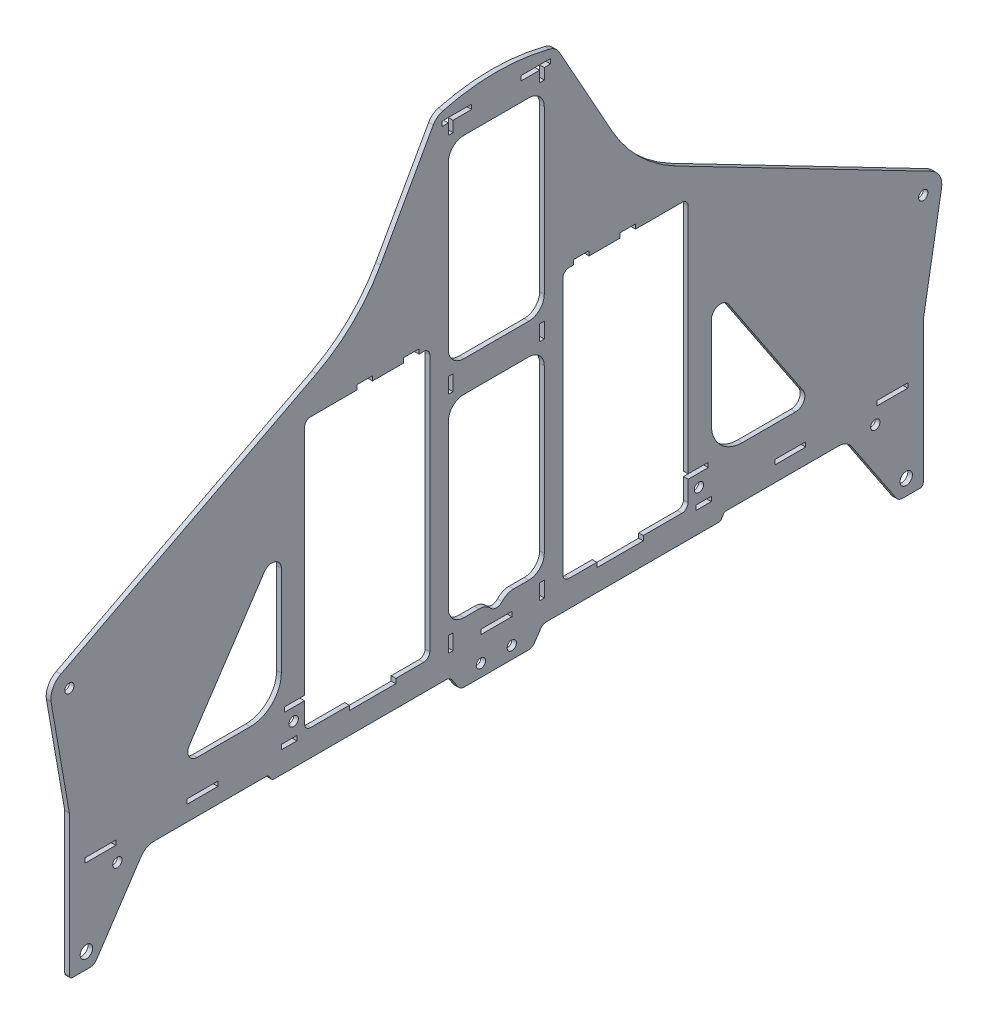
SolidWorks part; units mm, degrees
material "1023 Arkusz stali węglowej (SS)"
ref_plane "Płaszczyzna przednia" through (0, 0, 0) normal (0, 0, 1) x (1, 0, 0)
ref_plane "Płaszczyzna górna" through (0, 0, 0) normal (0, 1, 0) x (1, 0, 0)
ref_plane "Płaszczyzna prawa" through (0, 0, 0) normal (1, 0, 0) x (0, 0, -1)
sketch "Szkic1" plane through (0, 0, 0) normal (1, 0, 0) x (0, 0, -1)
  line L0 (-28.5915, -81.3449) -> (-24.8935, -86.8919)
  line L1 (-20.7333, -89.1184) -> (-0.0759, -89.1184)
  line L2 (-221.3907, -75.1184) -> (-148.664, -75.1184)
  line L3 (-143.8566, -79.1184) -> (-32.7518, -79.1184)
  line L4 (-145.5207, -78.2278) -> (-146.9999, -76.009)
  line L5 (-40.799, 235.6314) -> (-74.9912, 174.2495)
  line L6 (-276.0759, -123.1184) -> (-276.0759, -32.1184)
  line L7 (-258.5915, -122.8919) -> (-229.7112, -79.5714)
  line L8 (-274.0759, -125.1184) -> (-262.7518, -125.1184)
  line L9 (-116.3615, 134.116) -> (-281.5947, 48.5372)
  line L10 (-276.0759, -32.1184) -> (-287.9891, 36.4416)
  line L11 (-50.0759, 114.8816) -> (-50.0759, 111.8816)
  line L12 (-80.0759, 114.8816) -> (-80.0759, 111.8816)
  line L13 (-60.0759, 114.8816) -> (-60.0759, 111.8816)
  line L14 (-129.0759, -62.1184) -> (-129.0759, -65.1184)
  line L15 (-139.0759, -62.1184) -> (-139.0759, -65.1184)
  line L16 (-137.0759, -42.1184) -> (-124.0759, -42.1184)
  line L17 (-137.0759, -45.1184) -> (-124.0759, -45.1184)
  line L18 (-137.0759, -42.1184) -> (-137.0759, -45.1184)
  line L19 (-60.0759, 114.8816) -> (-50.0759, 114.8816)
  line L20 (-90.0759, 111.8816) -> (-90.0759, 114.8816)
  line L21 (-90.0759, 114.8816) -> (-80.0759, 114.8816)
  line L22 (-139.0759, -62.1184) -> (-129.0759, -62.1184)
  line L23 (-139.0759, -65.1184) -> (-129.0759, -65.1184)
  line L24 (-95.0759, -65.1184) -> (-65.0759, -65.1184)
  line L25 (-95.0759, -62.1184) -> (-95.0759, -65.1184)
  line L26 (-65.0759, -65.1184) -> (-65.0759, -62.1184)
  line L27 (-10.0759, -62.1184) -> (-10.0759, -65.1184)
  line L28 (-0.0759, -62.1184) -> (-10.0759, -62.1184)
  line L29 (-10.0759, -65.1184) -> (-0.0759, -65.1184)
  line L30 (-266.0759, -62.1184) -> (-266.0759, -65.1184)
  line L31 (-246.0759, -62.1184) -> (-246.0759, -65.1184)
  line L32 (-266.0759, -65.1184) -> (-246.0759, -65.1184)
  line L33 (-266.0759, -62.1184) -> (-246.0759, -62.1184)
  line L34 (-35.0759, 234.8816) -> (-16.0759, 234.8816)
  line L35 (-28.0759, 231.8816) -> (-16.0759, 231.8816)
  line L36 (-31.0759, 231.8816) -> (-31.0759, 224.8816)
  line L37 (-16.0759, 234.8816) -> (-16.0759, 231.8816)
  line L38 (-28.0759, 224.8816) -> (-31.0759, 224.8816)
  line L39 (-28.0759, 231.8816) -> (-28.0759, 224.8816)
  line L40 (-21.0759, -50.1184) -> (-11.2562, -50.1184)
  line L41 (-31.0759, 64.8816) -> (-31.0759, -40.1184)
  line L42 (-0.0759, 219.8816) -> (-21.0759, 219.8816)
  line L43 (-31.0759, 209.8816) -> (-31.0759, 104.8816)
  line L44 (-0.0759, 74.8816) -> (-21.0759, 74.8816)
  line L45 (-21.0759, 94.8816) -> (-0.0759, 94.8816)
  line L46 (-159.0759, -42.1184) -> (-193.5314, -42.1184)
  line L47 (-139.0759, 36.5649) -> (-139.0759, -22.1184)
  line L48 (-198.5237, -32.7902) -> (-150.0682, 39.8931)
  line L49 (-35.0759, 231.8816) -> (-31.0759, 231.8816)
  line L50 (-35.0759, 234.8816) -> (-35.0759, 231.8816)
  line L51 (28.4398, -81.3449) -> (24.7418, -86.8919)
  line L52 (20.5816, -89.1184) -> (-0.0759, -89.1184)
  line L53 (221.239, -75.1184) -> (148.5123, -75.1184)
  line L54 (143.7049, -79.1184) -> (32.6001, -79.1184)
  line L55 (145.369, -78.2278) -> (146.8482, -76.009)
  line L56 (40.6473, 235.6314) -> (74.8395, 174.2495)
  line L57 (275.9241, -123.1184) -> (275.9241, -32.1184)
  line L58 (258.4398, -122.8919) -> (229.5595, -79.5714)
  line L59 (273.9241, -125.1184) -> (262.6001, -125.1184)
  line L60 (116.2098, 134.116) -> (281.443, 48.5372)
  line L61 (275.9241, -32.1184) -> (287.8374, 36.4416)
  line L62 (49.9241, 114.8816) -> (49.9241, 111.8816)
  line L63 (79.9241, 114.8816) -> (79.9241, 111.8816)
  line L64 (59.9241, 114.8816) -> (59.9241, 111.8816)
  line L65 (128.9241, -62.1184) -> (128.9241, -65.1184)
  line L66 (138.9241, -62.1184) -> (138.9241, -65.1184)
  line L67 (136.9241, -42.1184) -> (123.9241, -42.1184)
  line L68 (136.9241, -45.1184) -> (123.9241, -45.1184)
  line L69 (136.9241, -42.1184) -> (136.9241, -45.1184)
  line L70 (59.9241, 114.8816) -> (49.9241, 114.8816)
  line L71 (89.9241, 111.8816) -> (89.9241, 114.8816)
  line L72 (89.9241, 114.8816) -> (79.9241, 114.8816)
  line L73 (138.9241, -62.1184) -> (128.9241, -62.1184)
  line L74 (138.9241, -65.1184) -> (128.9241, -65.1184)
  line L75 (94.9241, -65.1184) -> (64.9241, -65.1184)
  line L76 (94.9241, -62.1184) -> (94.9241, -65.1184)
  line L77 (64.9241, -65.1184) -> (64.9241, -62.1184)
  line L78 (9.9241, -62.1184) -> (9.9241, -65.1184)
  line L79 (-0.0759, -62.1184) -> (9.9241, -62.1184)
  line L80 (9.9241, -65.1184) -> (-0.0759, -65.1184)
  line L81 (265.9241, -62.1184) -> (265.9241, -65.1184)
  line L82 (245.9241, -62.1184) -> (245.9241, -65.1184)
  line L83 (265.9241, -65.1184) -> (245.9241, -65.1184)
  line L84 (265.9241, -62.1184) -> (245.9241, -62.1184)
  line L85 (34.9241, 234.8816) -> (15.9241, 234.8816)
  line L86 (27.9241, 231.8816) -> (15.9241, 231.8816)
  line L87 (30.9241, 231.8816) -> (30.9241, 224.8816)
  line L88 (15.9241, 234.8816) -> (15.9241, 231.8816)
  line L89 (27.9241, 224.8816) -> (30.9241, 224.8816)
  line L90 (27.9241, 231.8816) -> (27.9241, 224.8816)
  line L91 (20.9241, -50.1184) -> (11.1045, -50.1184)
  line L92 (30.9241, 64.8816) -> (30.9241, -40.1184)
  line L93 (-0.0759, 219.8816) -> (20.9241, 219.8816)
  line L94 (30.9241, 209.8816) -> (30.9241, 104.8816)
  line L95 (-0.0759, 74.8816) -> (20.9241, 74.8816)
  line L96 (20.9241, 94.8816) -> (-0.0759, 94.8816)
  line L97 (158.9241, -42.1184) -> (193.3797, -42.1184)
  line L98 (138.9241, 36.5649) -> (138.9241, -22.1184)
  line L99 (198.372, -32.7902) -> (149.9164, 39.8931)
  line L100 (34.9241, 231.8816) -> (30.9241, 231.8816)
  line L101 (34.9241, 234.8816) -> (34.9241, 231.8816)
  line L438 (-124.0759, -45.1184) -> (-124.0759, -58.1184)
  line L439 (-120.0759, -62.1184) -> (-95.0759, -62.1184)
  line L440 (-90.0759, 111.8816) -> (-120.0759, 111.8816)
  line L441 (-124.0759, 107.8816) -> (-124.0759, -42.1184)
  line L442 (-60.0759, 111.8816) -> (-80.0759, 111.8816)
  line L443 (-65.0759, -62.1184) -> (-47.0759, -62.1184)
  line L444 (-43.0759, -58.1184) -> (-43.0759, 107.8816)
  line L445 (-47.0759, 111.8816) -> (-50.0759, 111.8816)
  line L446 (-200.0759, -62.1184) -> (-200.0759, -65.1184)
  line L447 (-200.0759, -65.1184) -> (-180.0759, -65.1184)
  line L448 (-180.0759, -65.1184) -> (-180.0759, -62.1184)
  line L449 (-180.0759, -62.1184) -> (-200.0759, -62.1184)
  line L450 (-31.0759, -55.1184) -> (-31.0759, -65.1184)
  line L451 (-31.0759, -65.1184) -> (-28.0759, -65.1184)
  line L452 (-28.0759, -65.1184) -> (-28.0759, -55.1184)
  line L453 (-28.0759, -55.1184) -> (-31.0759, -55.1184)
  line L454 (-31.0759, 89.8816) -> (-31.0759, 79.8816)
  line L455 (-31.0759, 79.8816) -> (-28.0759, 79.8816)
  line L456 (-28.0759, 79.8816) -> (-28.0759, 89.8816)
  line L457 (-28.0759, 89.8816) -> (-31.0759, 89.8816)
  line L458 (123.9241, -45.1184) -> (123.9241, -58.1184)
  line L459 (119.9241, -62.1184) -> (94.9241, -62.1184)
  line L460 (89.9241, 111.8816) -> (119.9241, 111.8816)
  line L461 (123.9241, 107.8816) -> (123.9241, -42.1184)
  line L462 (59.9241, 111.8816) -> (79.9241, 111.8816)
  line L463 (64.9241, -62.1184) -> (46.9241, -62.1184)
  line L464 (42.9241, -58.1184) -> (42.9241, 107.8816)
  line L465 (46.9241, 111.8816) -> (49.9241, 111.8816)
  line L466 (199.9241, -62.1184) -> (199.9241, -65.1184)
  line L467 (199.9241, -65.1184) -> (179.9241, -65.1184)
  line L468 (179.9241, -65.1184) -> (179.9241, -62.1184)
  line L469 (179.9241, -62.1184) -> (199.9241, -62.1184)
  line L470 (30.9241, -55.1184) -> (30.9241, -65.1184)
  line L471 (30.9241, -65.1184) -> (27.9241, -65.1184)
  line L472 (27.9241, -65.1184) -> (27.9241, -55.1184)
  line L473 (27.9241, -55.1184) -> (30.9241, -55.1184)
  line L474 (30.9241, 89.8816) -> (30.9241, 79.8816)
  line L475 (30.9241, 79.8816) -> (27.9241, 79.8816)
  line L476 (27.9241, 79.8816) -> (27.9241, 89.8816)
  line L477 (27.9241, 89.8816) -> (30.9241, 89.8816)
  arc A0 (-28.5915, -81.3449) -> (-32.7518, -79.1184) centre (-32.7518, -84.1184) ccw
  arc A1 (-24.8935, -86.8919) -> (-20.7333, -89.1184) centre (-20.7333, -84.1184) ccw
  arc A2 (-146.9999, -76.009) -> (-148.664, -75.1184) centre (-148.664, -77.1184) ccw
  arc A3 (-145.5207, -78.2278) -> (-143.8566, -79.1184) centre (-143.8566, -77.1184) ccw
  arc A4 (-221.3907, -75.1184) -> (-229.7112, -79.5714) centre (-221.3907, -85.1184) ccw
  circle A5 centre (-10.0759, -81.1184) radius 3
  circle A6 centre (-265.0759, -115.1184) radius 4
  arc A7 (-276.0759, -123.1184) -> (-274.0759, -125.1184) centre (-274.0759, -123.1184) ccw
  arc A8 (-262.7518, -125.1184) -> (-258.5915, -122.8919) centre (-262.7518, -120.1184) ccw
  arc A9 (-281.5947, 48.5372) -> (-287.7766, 35.2183) centre (-276.0759, 37.8816) ccw
  circle A10 centre (-276.0759, 37.8816) radius 3
  arc A11 (-116.3615, 134.116) -> (-74.9912, 174.2495) centre (-162.3518, 222.9129) ccw
  circle A12 centre (-131.0759, -53.1184) radius 3
  arc A13 (-0.0759, 244.8816) -> (-34.5949, 240.4392) centre (-0.0759, 108.5483) ccw
  arc A14 (-34.5949, 240.4392) -> (-40.799, 235.6314) centre (-32.063, 230.765) ccw
  arc A15 (-31.0759, 104.8816) -> (-21.0759, 94.8816) centre (-21.0759, 104.8816) ccw
  arc A16 (-21.0759, 74.8816) -> (-31.0759, 64.8816) centre (-21.0759, 64.8816) ccw
  arc A17 (-21.0759, 219.8816) -> (-31.0759, 209.8816) centre (-21.0759, 209.8816) ccw
  arc A18 (-31.0759, -40.1184) -> (-21.0759, -50.1184) centre (-21.0759, -40.1184) ccw
  arc A19 (-159.0759, -42.1184) -> (-139.0759, -22.1184) centre (-159.0759, -22.1184) ccw
  arc A20 (-198.5237, -32.7902) -> (-193.5314, -42.1184) centre (-193.5314, -36.1184) ccw
  arc A21 (-139.0759, 36.5649) -> (-150.0682, 39.8931) centre (-145.0759, 36.5649) ccw
  arc A22 (-3.8026, -53.4517) -> (-11.2562, -50.1184) centre (-11.2562, -60.1184) ccw
  arc A23 (-3.8026, -53.4517) -> (-0.0759, -55.1184) centre (-0.0759, -50.1184) ccw
  circle A24 centre (-245.0759, -75.1184) radius 3
  arc A25 (32.6001, -79.1184) -> (28.4398, -81.3449) centre (32.6001, -84.1184) ccw
  arc A26 (20.5816, -89.1184) -> (24.7418, -86.8919) centre (20.5816, -84.1184) ccw
  arc A27 (148.5123, -75.1184) -> (146.8482, -76.009) centre (148.5123, -77.1184) ccw
  arc A28 (143.7049, -79.1184) -> (145.369, -78.2278) centre (143.7049, -77.1184) ccw
  arc A29 (229.5595, -79.5714) -> (221.239, -75.1184) centre (221.239, -85.1184) ccw
  circle A30 centre (9.9241, -81.1184) radius 3
  circle A31 centre (264.9241, -115.1184) radius 4
  arc A32 (273.9241, -125.1184) -> (275.9241, -123.1184) centre (273.9241, -123.1184) ccw
  arc A33 (258.4398, -122.8919) -> (262.6001, -125.1184) centre (262.6001, -120.1184) ccw
  arc A34 (287.6249, 35.2183) -> (281.443, 48.5372) centre (275.9241, 37.8816) ccw
  circle A35 centre (275.9241, 37.8816) radius 3
  arc A36 (74.8395, 174.2495) -> (116.2098, 134.116) centre (162.2001, 222.9129) ccw
  circle A37 centre (130.9241, -53.1184) radius 3
  arc A38 (34.4432, 240.4392) -> (-0.0759, 244.8816) centre (-0.0759, 108.5483) ccw
  arc A39 (40.6473, 235.6314) -> (34.4432, 240.4392) centre (31.9113, 230.765) ccw
  arc A40 (20.9241, 94.8816) -> (30.9241, 104.8816) centre (20.9241, 104.8816) ccw
  arc A41 (30.9241, 64.8816) -> (20.9241, 74.8816) centre (20.9241, 64.8816) ccw
  arc A42 (30.9241, 209.8816) -> (20.9241, 219.8816) centre (20.9241, 209.8816) ccw
  arc A43 (20.9241, -50.1184) -> (30.9241, -40.1184) centre (20.9241, -40.1184) ccw
  arc A44 (138.9241, -22.1184) -> (158.9241, -42.1184) centre (158.9241, -22.1184) ccw
  arc A45 (193.3797, -42.1184) -> (198.372, -32.7902) centre (193.3797, -36.1184) ccw
  arc A46 (149.9164, 39.8931) -> (138.9241, 36.5649) centre (144.9241, 36.5649) ccw
  arc A47 (11.1045, -50.1184) -> (3.6509, -53.4517) centre (11.1045, -60.1184) ccw
  arc A48 (-0.0759, -55.1184) -> (3.6509, -53.4517) centre (-0.0759, -50.1184) ccw
  circle A49 centre (244.9241, -75.1184) radius 3
  arc A194 (-124.0759, -58.1184) -> (-120.0759, -62.1184) centre (-120.0759, -58.1184) ccw
  arc A195 (-120.0759, 111.8816) -> (-124.0759, 107.8816) centre (-120.0759, 107.8816) ccw
  arc A196 (-47.0759, -62.1184) -> (-43.0759, -58.1184) centre (-47.0759, -58.1184) ccw
  arc A197 (-43.0759, 107.8816) -> (-47.0759, 111.8816) centre (-47.0759, 107.8816) ccw
  arc A198 (119.9241, -62.1184) -> (123.9241, -58.1184) centre (119.9241, -58.1184) ccw
  arc A199 (123.9241, 107.8816) -> (119.9241, 111.8816) centre (119.9241, 107.8816) ccw
  arc A200 (42.9241, -58.1184) -> (46.9241, -62.1184) centre (46.9241, -58.1184) ccw
  arc A201 (46.9241, 111.8816) -> (42.9241, 107.8816) centre (46.9241, 107.8816) ccw
extrude "Dodanie-wyciągnięcie1" add sketch "Szkic1" along normal blind 3 contours L56 A39 A38 A13 A14 L5 A11 L9 A9 L10 L6 A7 L8 A8 L7 A4 L2 A2 L4 A3 L3 A0 L0 A1 L1 L52 A26 L51 A25 L54 A28 L55 A27 L53 A29 L58 A33 L59 A32 L57 L61 A34 L60 A36 A201 L465 L62 L70 region at (0, -73.6741, 27.1621)
